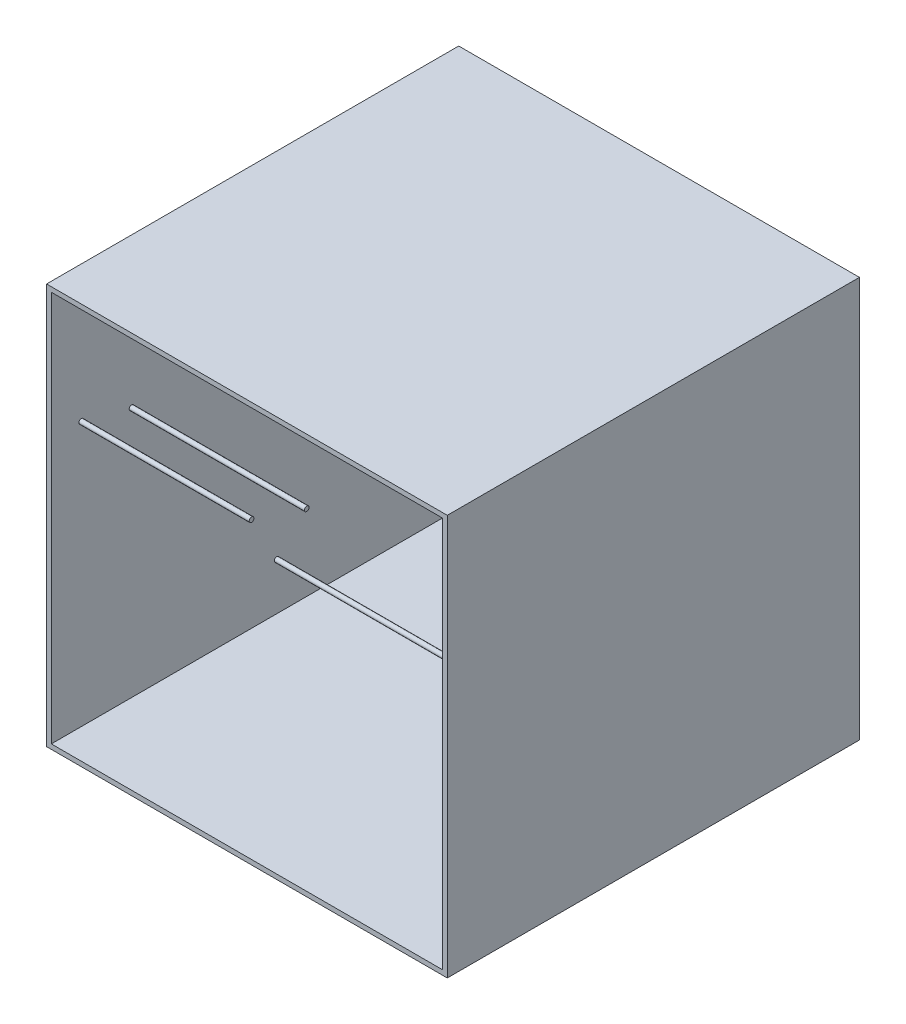
SolidWorks part; units mm, degrees
ref_plane "Plano frontal" through (0, 0, 0) normal (0, 0, 1) x (1, 0, 0)
ref_plane "Plano superior" through (0, 0, 0) normal (0, 1, 0) x (1, 0, 0)
ref_plane "Plano direito" through (0, 0, 0) normal (1, 0, 0) x (0, 0, -1)
sketch "Esboço1" plane through (0, 0, 0) normal (0, 0, 1) x (1, 0, 0)
  line L1 (-210, 210) -> (210, 210)
  line L2 (-210, 210) -> (-210, -210)
  line L3 (-210, -210) -> (210, -210)
  line L4 (210, 210) -> (210, -210)
  line L5 (205, -205) -> (-205, -205)
  line L6 (205, -205) -> (205, 205)
  line L7 (205, 205) -> (-205, 205)
  line L8 (-205, -205) -> (-205, 205)
  line L9 (205, -205) -> (-205, 205) construction
  line L10 (205, 205) -> (-205, -205) construction
  point P4 (-210, 0)
  point P6 (0, 210)
  point P7 (0, 0)
  dimension "D1" = 420
  dimension "D2" = 420
  dimension "D3" = 410
  dimension "D4" = 410
extrude "Ressalto-extrusão1" add sketch "Esboço1" along normal blind 432
sketch "Esboço4" plane through (-210, 0, 0) normal (-1, 0, 0) x (0, 0, 1)
  line L0 (0, 58.16) -> (347.87, 58.16) construction
  line L1 (0, 210) -> (0, -210) construction
  line L2 (347.87, 58.16) -> (347.87, -210) construction
  line L4 (0, 72.17) -> (400.68, 72.17) construction
  line L5 (400.68, 72.17) -> (400.68, -210) construction
  line L6 (0, -10.05) -> (153.03, -10.05) construction
  line L7 (153.03, -10.05) -> (153.03, -210) construction
  line L8 (432, -210) -> (0, -210) construction
  circle A0 centre (153.03, -10.05) radius 15
  circle A1 centre (347.87, 58.16) radius 2.5
  circle A2 centre (400.68, 72.17) radius 2.5
  dimension "D1" = 153.03
  dimension "D2" = 199.95
  dimension "D3" = 347.87
  dimension "D4" = 268.16
  dimension "D5" = 400.68
  dimension "D6" = 282.17
extrude "Ressalto-extrusão4" add sketch "Esboço4" against normal blind 183.55 contours A2 region at (-210, 72.17, 400.68)
extrude "Ressalto-extrusão5" add sketch "Esboço4<4>" against normal blind 188.55 contours A1
sketch "Esboço4<4>" plane through (-210, 0, 0) normal (-1, 0, 0) x (0, 0, 1) same geometry as "Esboço4"
sketch "Esboço5" plane through (210, 0, 0) normal (1, 0, 0) x (0, 0, -1)
  line L0 (0, 138.09) -> (-353.49, 138.09) construction
  line L1 (0, -210) -> (0, 210) construction
  line L2 (-353.49, 138.09) -> (-353.49, -210) construction
  line L3 (-432, -210) -> (0, -210) construction
  line L4 (0, 75.92) -> (-427.35, 75.92) construction
  line L5 (-427.35, 75.92) -> (-427.35, -210) construction
  circle A0 centre (-353.49, 138.09) radius 2.5
  circle A1 centre (-427.35, 75.92) radius 2.5
  dimension "D1" = 353.49
  dimension "D2" = 348.09
  dimension "D3" = 427.35
  dimension "D4" = 285.92
extrude "Ressalto-extrusão6" add sketch "Esboço5" against normal blind 183.45
sketch "Esboço6" plane through (-210, 0, 0) normal (-1, 0, 0) x (0, 0, 1)
  line L0 (0, -10.05) -> (150.03, -10.05) construction
  line L1 (0, 210) -> (0, -210) construction
  line L2 (150.03, -10.05) -> (150.03, -210) construction
  line L3 (432, -210) -> (0, -210) construction
  circle A0 centre (150.03, -10.05) radius 15
  dimension "D1" = 150.03
  dimension "D2" = 199.95
extrude "Ressalto-extrusão7" add sketch "Esboço6" against normal blind 183.45
